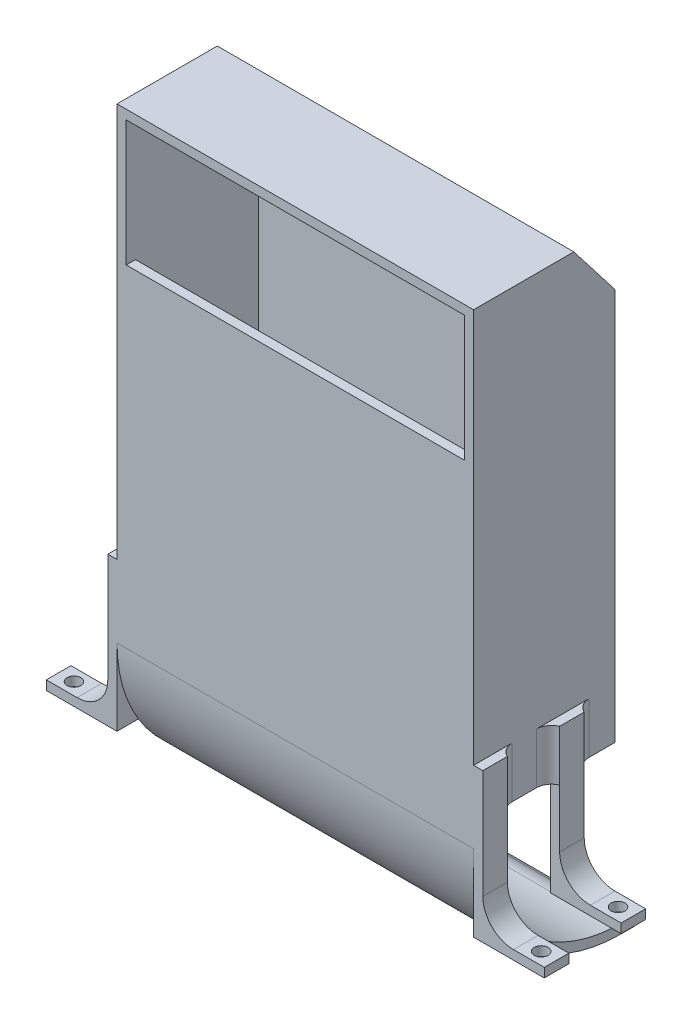
SolidWorks part; units mm, degrees
ref_plane "Front Plane" through (0, 0, 0) normal (0, 0, 1) x (1, 0, 0)
ref_plane "Top Plane" through (0, 0, 0) normal (0, 1, 0) x (1, 0, 0)
ref_plane "Right Plane" through (0, 0, 0) normal (1, 0, 0) x (0, 0, -1)
sketch "Sketch1" plane through (0, 0, 0) normal (1, 0, 0) x (0, 0, -1)
  line L0 (0, 0) -> (0, 108)
  line L1 (3, 0) -> (3, 108)
  line L2 (48, -45) -> (52.3715, -48)
  line L3 (52.3715, -48) -> (48, -48)
  line L4 (3, 108) -> (0, 108)
  arc A0 (0, 0) -> (48, -48) centre (48, 0) ccw
  arc A1 (3, 0) -> (48, -45) centre (48, 0) ccw
  dimension "D2" = 45
  dimension "D3" = 108
  dimension "D1" = 3
extrude "Boss-Extrude1" add sketch "Sketch1" along normal blind 116
sketch "Sketch2" plane through (0, 0, -3) normal (0, 0, -1) x (-1, 0, 0)
  line L1 (-116, 108) -> (-113, 108)
  line L2 (-116, 108) -> (-116, 6.9609)
  line L3 (-116, 6.9609) -> (-113, 6.9609)
  line L4 (-113, 108) -> (-113, 6.9609)
  line L5 (0, 0) -> (0, 108) construction
  line L6 (0, 108) -> (-3, 108)
  line L7 (0, 108) -> (0, 6.9609)
  line L8 (0, 6.9609) -> (-3, 6.9609)
  line L9 (-3, 108) -> (-3, 6.9609)
  line L10 (-116, 108) -> (0, 108) construction
  dimension "D1" = 3
  dimension "D2" = 3
extrude "Boss-Extrude2" add sketch "Sketch2" along normal blind 40
sketch "Sketch3" plane through (0, 0, -43) normal (0, 0, -1) x (-1, 0, 0)
  line L1 (-116, 108) -> (0, 108)
  line L2 (-116, 108) -> (-116, 6.9609)
  line L3 (-116, 6.9609) -> (0, 6.9609)
  line L4 (0, 108) -> (0, 6.9609)
extrude "Boss-Extrude3" add sketch "Sketch3" along normal blind 3
sketch "Sketch5" plane through (116, 0, 0) normal (1, 0, 0) x (0, 0, -1)
  line L0 (43, 134.156) -> (31.6048, 148.8762)
  line L1 (46, 108) -> (46, 134.5949)
  line L2 (31.6048, 148.8762) -> (0, 148.8762)
  line L3 (0, 148.8762) -> (0, 151.8762)
  line L4 (0, 151.8762) -> (32.6221, 151.8762)
  line L5 (32.6221, 151.8762) -> (46, 134.5949)
  line L6 (0, 108) -> (0, 0) construction
  line L7 (43, 134.156) -> (43, 108)
  line L8 (46, 108) -> (0, 108) construction
  line L9 (43, 108) -> (46, 108)
  dimension "D1" = 3
  dimension "D2" = 3
extrude "Boss-Extrude4" add sketch "Sketch5" against normal blind 116
sketch "Sketch6" plane through (116, 0, 0) normal (1, 0, 0) x (0, 0, -1)
  line L2 (0, 148.8762) -> (31.6048, 148.8762) construction
  line L5 (0, 148.8762) -> (31.6048, 148.8762)
  line L6 (0, 148.8762) -> (0, 108)
  line L7 (43, 108) -> (0, 108) construction
  line L8 (43, 134.156) -> (43, 108) construction
  line L9 (31.6048, 148.8762) -> (43, 134.156) construction
  line L10 (43, 108) -> (0, 108)
  line L11 (43, 134.156) -> (43, 108)
  line L12 (31.6048, 148.8762) -> (43, 134.156)
extrude "Boss-Extrude5" add sketch "Sketch6" against normal blind 3
sketch "Sketch7" plane through (0, 0, 0) normal (-1, 0, 0) x (0, 0, 1)
  line L8 (-31.6048, 148.8762) -> (0, 148.8762) construction
  line L9 (-43, 134.156) -> (-31.6048, 148.8762) construction
  line L10 (0, 148.8762) -> (0, 108) construction
  line L11 (-31.6048, 148.8762) -> (0, 148.8762)
  line L12 (-43, 134.156) -> (-31.6048, 148.8762)
  line L13 (0, 148.8762) -> (0, 108)
  line L14 (0, 108) -> (-43, 108)
  line L15 (-43, 108) -> (-43, 134.156)
extrude "Boss-Extrude6" add sketch "Sketch7" against normal blind 3
sketch "Sketch8" plane through (0, 0, 0) normal (-1, 0, 0) x (0, 0, 1)
  line L0 (-46, 6.9609) -> (-3, 6.9609) construction
  line L1 (-8, 23.5177) -> (0, 23.5177)
  line L2 (-8, 23.5177) -> (-8, 6.9609)
  line L3 (-8, 6.9609) -> (0, 6.9609)
  line L4 (0, 23.5177) -> (0, 6.9609)
  line L5 (0, 151.8762) -> (0, 0) construction
  dimension "D1" = 8
extrude "Boss-Extrude7" add sketch "Sketch8" along normal blind 3
sketch "Sketch9" plane through (0, 6.9609, 0) normal (0, -1, 0) x (1, 0, 0)
  line L1 (-3, -8) -> (0, -8)
  line L2 (-3, -8) -> (-3, 0)
  line L3 (-3, 0) -> (0, 0)
  line L4 (0, -8) -> (0, 0)
extrude "Boss-Extrude8" add sketch "Sketch9" along normal blind 31.86
sketch "Sketch10" plane through (-3, 0, 0) normal (-1, 0, 0) x (0, 0, 1)
  line L0 (0, -24.8991) -> (0, 23.5177) construction
  line L1 (-8, -24.8991) -> (0, -24.8991)
  line L2 (-8, -24.8991) -> (-8, -21.8991)
  line L3 (-8, -21.8991) -> (0, -21.8991)
  line L4 (0, -24.8991) -> (0, -21.8991)
  dimension "D1" = 3
extrude "Boss-Extrude9" add sketch "Sketch10" along normal blind 20
sketch "Sketch12" plane through (0, 23.5177, 0) normal (0, 1, 0) x (1, 0, 0)
  line L0 (0, 0) -> (0, 8) construction
  line L1 (0, 25) -> (-3, 25)
  line L2 (0, 25) -> (0, 33)
  line L3 (0, 33) -> (-3, 33)
  line L4 (-3, 25) -> (-3, 33)
  line L5 (-3, 8) -> (0, 8) construction
  dimension "D1" = 3
  dimension "D2" = 8
  dimension "D3" = 17
extrude "Boss-Extrude10" add sketch "Sketch12" against normal blind 48.42 separate body
sketch "Sketch13" plane through (0, -24.9023, 0) normal (0, -1, 0) x (1, 0, 0)
  line L0 (-23, -8) -> (-23, 0) construction
  line L1 (0, -33) -> (-23, -33)
  line L2 (0, -33) -> (0, -25)
  line L3 (0, -25) -> (-23, -25)
  line L4 (-23, -33) -> (-23, -25)
  dimension "D1" = 8
extrude "Boss-Extrude11" add sketch "Sketch13" against normal blind 3
fillet "Fillet2" radius 10 2 edges at (-3, -21.8991, -4) (-3, -21.9023, -29)
sketch "Sketch14" plane through (0, 23.5177, 0) normal (0, 1, 0) x (1, 0, 0)
  line L1 (116, 0) -> (119, 0)
  line L2 (116, 0) -> (116, 8)
  line L3 (116, 8) -> (119, 8)
  line L4 (119, 0) -> (119, 8)
  line L5 (116, 33) -> (119, 33)
  line L6 (116, 33) -> (116, 25)
  line L7 (116, 25) -> (119, 25)
  line L8 (119, 33) -> (119, 25)
  line L9 (116, 0) -> (0, 0) construction
  line L10 (116, 32.6221) -> (116, 0) construction
  point P8 (117.5, 25)
  dimension "D1" = 3
  dimension "D2" = 3
  dimension "D3" = 8
  dimension "D4" = 8
  dimension "D5" = 17
extrude "Boss-Extrude12" add sketch "Sketch14" against normal blind 48.42
sketch "Sketch15" plane through (119, 0, 0) normal (1, 0, 0) x (0, 0, -1)
  line L0 (25, -24.9023) -> (25, 23.5177) construction
  line L1 (33, -24.9023) -> (25, -24.9023)
  line L2 (33, -24.9023) -> (33, -21.9023)
  line L3 (33, -21.9023) -> (25, -21.9023)
  line L4 (25, -24.9023) -> (25, -21.9023)
  line L5 (0, -24.9023) -> (0, 23.5177) construction
  line L6 (8, -24.9023) -> (0, -24.9023)
  line L7 (8, -24.9023) -> (8, -21.9023)
  line L8 (8, -21.9023) -> (0, -21.9023)
  line L9 (0, -24.9023) -> (0, -21.9023)
  dimension "D1" = 3
  dimension "D2" = 3
extrude "Boss-Extrude13" add sketch "Sketch15" along normal blind 20
fillet "Fillet3" radius 10 2 edges at (119, -21.9023, -29) (119, -21.9023, -4)
sketch "Sketch11" plane through (0, -21.8991, 0) normal (0, 1, 0) x (1, 0, 0)
  line L0 (-23, 0) -> (-23, 8) construction
  line L1 (-23, 25) -> (-23, 33) construction
  line L2 (139, 8) -> (139, 0) construction
  line L3 (139, 33) -> (139, 25) construction
  line L4 (139, 0) -> (129, 0) construction
  line L5 (139, 25) -> (129, 25) construction
  line L6 (-23, 0) -> (-13, 0) construction
  line L7 (-13, 25) -> (-23, 25) construction
  circle A0 centre (-18, 4) radius 2.25
  circle A1 centre (-18, 29) radius 2.25
  circle A2 centre (134, 4) radius 2.25
  circle A3 centre (134, 29) radius 2.25
  point P5 (-23, 4)
  point P9 (-23, 29)
  point P16 (139, 4)
  point P19 (139, 29)
  point P22 (134, 0)
  point P25 (134, 25)
  point P28 (-18, 0)
  point P29 (0, 0)
  point P32 (-18, 25)
  dimension "D1" = 4.5
  dimension "D2" = 4.5
  dimension "D3" = 4.5
  dimension "D4" = 4.5
extrude "Cut-Extrude1" cut sketch "Sketch11" against normal blind 20
fillet "Fillet5" radius 5 6 edges at (0, 15.2393, -25) (0, 15.2393, -8) (0, 15.2393, -33) (116, 15.2393, -8) (116, 15.2393, -33) (116, 15.2393, -25)
fillet "Fillet6" radius 10 1 edges at (58, -45, -48)
